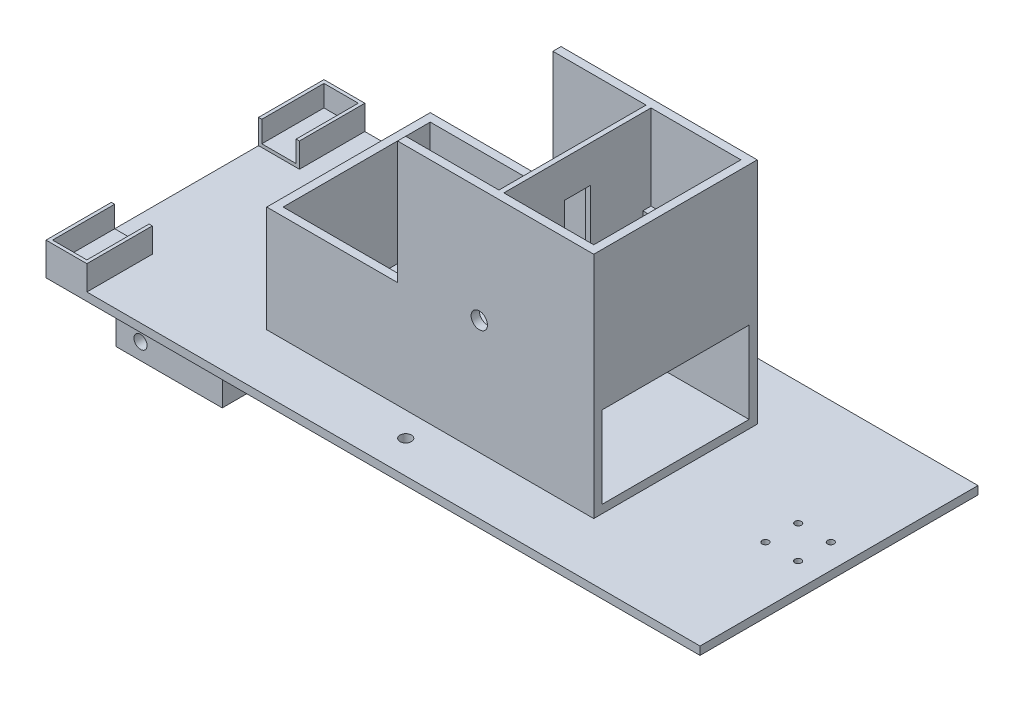
SolidWorks part; units mm, degrees
ref_plane "Front Plane" through (0, 0, 0) normal (0, 0, 1) x (1, 0, 0)
ref_plane "Top Plane" through (0, 0, 0) normal (0, 1, 0) x (1, 0, 0)
ref_plane "Right Plane" through (0, 0, 0) normal (1, 0, 0) x (0, 0, -1)
sketch "Sketch1" plane through (0, 0, 0) normal (0, 1, 0) x (1, 0, 0)
  line L1 (200, -85) -> (-200, -85)
  line L2 (200, -85) -> (200, 85)
  line L3 (200, 85) -> (-200, 85)
  line L4 (-200, -85) -> (-200, 85)
  line L5 (200, -85) -> (-200, 85) construction
  line L6 (200, 85) -> (-200, -85) construction
  point P0 (0, 0)
  dimension "D1" = 170
  dimension "D2" = 400
extrude "Boss-Extrude1" add sketch "Sketch1" along normal blind 5
sketch "Sketch2" plane through (0, 5, 0) normal (0, 1, 0) x (1, 0, 0)
  line L0 (-200, 85) -> (-200, -85) construction
  line L1 (100, -50) -> (-100, -50)
  line L2 (100, -50) -> (100, 50)
  line L3 (100, 50) -> (-100, 50)
  line L4 (-100, -50) -> (-100, 50)
  line L5 (100, -50) -> (-100, 50) construction
  line L6 (100, 50) -> (-100, -50) construction
  point P0 (0, 0)
  dimension "D1" = 200
  dimension "D2" = 100
  dimension "D3" = 200
extrude "Boss-Extrude2" add sketch "Sketch2" along normal blind 140
shell "Shell1" thickness 5 removed face at (0, 145, 0)
sketch "Sketch3" plane through (0, 0, 50) normal (0, 0, 1) x (1, 0, 0)
  line L1 (-100, 145) -> (-20, 145)
  line L2 (-100, 145) -> (-100, 70)
  line L3 (-100, 70) -> (-20, 70)
  line L4 (-20, 145) -> (-20, 70)
  dimension "D1" = 80
  dimension "D2" = 75
extrude "Cut-Extrude1" cut sketch "Sketch3" against normal through all and the other way through all
sketch "Sketch4" plane through (0, 5, 0) normal (0, 1, 0) x (1, 0, 0)
  line L0 (-95, -45) -> (-95, 45) construction
  circle A0 centre (-40, 0) radius 10
  dimension "D1" = 55
extrude "Cut-Extrude2" cut sketch "Sketch4" against normal blind 140
sketch "Sketch5" plane through (0, 0, 50) normal (0, 0, 1) x (1, 0, 0)
  line L0 (-20, 145) -> (100, 145) construction
  line L1 (37, 145) -> (40, 145)
  line L2 (37, 145) -> (37, 5)
  line L3 (37, 5) -> (40, 5)
  line L4 (40, 145) -> (40, 5)
  line L5 (-100, 5) -> (100, 5) construction
  line L6 (100, 145) -> (100, 5) construction
  dimension "D1" = 3
  dimension "D2" = 60
extrude "Boss-Extrude3" add sketch "Sketch5" against normal up to surface (95 mm away) up to face at (-6.6667, 73.3333, -45)
sketch "Sketch6" plane through (37, 0, 0) normal (-1, 0, 0) x (0, 0, 1)
  line L0 (-45, 145) -> (45, 145) construction
  line L1 (8, 27.5) -> (-8, 27.5)
  line L2 (8, 27.5) -> (8, 122.5)
  line L3 (8, 122.5) -> (-8, 122.5)
  line L4 (-8, 27.5) -> (-8, 122.5)
  line L5 (8, 27.5) -> (-8, 122.5) construction
  line L6 (8, 122.5) -> (-8, 27.5) construction
  line L7 (-45, 5) -> (-45, 145) construction
  point P0 (0, 75)
  dimension "D1" = 16
  dimension "D2" = 95
  dimension "D3" = 70
  dimension "D4" = 37
extrude "Cut-Extrude3" cut sketch "Sketch6" against normal up to next
sketch "Sketch7" plane through (0, 0, 50) normal (0, 0, 1) x (1, 0, 0)
  line L0 (-100, 5) -> (100, 5) construction
  line L1 (-20, 145) -> (-20, 70) construction
  circle A0 centre (30, 75) radius 5
  dimension "D1" = 70
  dimension "D3" = 10
  dimension "D2" = 50
extrude "Cut-Extrude4" cut sketch "Sketch7" against normal blind 140
sketch "Sketch8" plane through (0, 0, 0) normal (0, -1, 0) x (1, 0, 0)
  line L1 (-162.2005, 80) -> (-97.2005, 80)
  line L2 (-162.2005, 80) -> (-162.2005, 55)
  line L3 (-162.2005, 55) -> (-97.2005, 55)
  line L4 (-97.2005, 80) -> (-97.2005, 55)
  line L5 (-200, 85) -> (200, 85) construction
  dimension "D1" = 25
  dimension "D2" = 5
  dimension "D3" = 65
extrude "Boss-Extrude4" add sketch "Sketch8" along normal blind 20
mirror "Mirror1" about plane through (0, 0, 0) normal (0, 0, 1) of "Boss-Extrude4"
sketch "Sketch9" plane through (0, 5, 0) normal (0, 1, 0) x (1, 0, 0)
  line L0 (200, -85) -> (200, 85) construction
  line L1 (-200, -85) -> (200, -85) construction
  circle A0 centre (185, 10) radius 2
  circle A1 centre (185, -10) radius 2
  circle A2 centre (165, -10) radius 2
  circle A3 centre (165, 10) radius 2
  dimension "D1" = 4
  dimension "D6" = 75
  dimension "D2" = 20
  dimension "D3" = 20
  dimension "D4" = 20
  dimension "D5" = 15
extrude "Cut-Extrude5" cut sketch "Sketch9" against normal blind 20
sketch "Sketch21" plane through (0, 5, 0) normal (0, 1, 0) x (1, 0, 0)
  line L0 (200, 85) -> (-200, 85) construction
  line L1 (-200, -85) -> (200, -85) construction
  circle A0 centre (0, 65) radius 3.5
  circle A1 centre (0, -65) radius 3.5
  dimension "D1" = 7
  dimension "D2" = 7
  dimension "D3" = 20
  dimension "D4" = 20
extrude "Cut-Extrude9" cut sketch "Sketch21" against normal through all
sketch "Sketch22" plane through (0, 0, 80) normal (0, 0, 1) x (1, 0, 0)
  line L0 (-162.2005, -20) -> (-162.2005, 0) construction
  circle A0 centre (-147.2005, -10) radius 4
  dimension "D1" = 8
  dimension "D2" = 15
extrude "Cut-Extrude10" cut sketch "Sketch22" against normal up to surface (160 mm away) up to face at (-129.7005, -10, -80)
sketch "Sketch35" plane through (100, 0, 0) normal (1, 0, 0) x (0, 0, -1)
  line L1 (-50, 145) -> (-50, 5) construction
  line L2 (-85, 5) -> (85, 5) construction
  line L3 (-45, 60) -> (45, 60)
  line L5 (-45, 60) -> (-45, 10)
  line L6 (-45, 10) -> (45, 10)
  line L7 (45, 10) -> (45, 60)
  dimension "D1" = 90
  dimension "D2" = 5
  dimension "D3" = 5
  dimension "D4" = 50
extrude "Cut-Extrude14" cut sketch "Sketch35" against normal blind 15
sketch "Sketch36" plane through (100, 0, 0) normal (1, 0, 0) x (0, 0, -1)
  line L0 (50, 145) -> (50, 5) construction
  line L1 (-50, 5) -> (50, 5)
  line L2 (-50, 5) -> (-50, 10)
  line L3 (-50, 10) -> (50, 10)
  line L4 (50, 5) -> (50, 10)
extrude "Boss-Extrude17" add sketch "Sketch36" against normal up to surface (60 mm away) up to face at (40, 75, 0)
sketch "Sketch38" plane through (0, 5, 0) normal (0, 1, 0) x (1, 0, 0)
  line L1 (-175, 85) -> (-200, 85)
  line L2 (-175, 85) -> (-175, 45)
  line L3 (-175, 45) -> (-200, 45)
  line L4 (-200, 85) -> (-200, 45)
  line L5 (-175, -85) -> (-200, -85)
  line L6 (-175, -85) -> (-175, -45)
  line L7 (-175, -45) -> (-200, -45)
  line L8 (-200, -85) -> (-200, -45)
  point P8 (0, 0)
  point P9 (-200, 85)
  point P10 (-162.9424, -80.3865)
  point P11 (-200, -85)
  point P12 (0, 0)
  dimension "D1" = 25
  dimension "D2" = 40
extrude "Boss-Extrude19" add sketch "Sketch38" along normal blind 15
sketch "Sketch39" plane through (0, 0, -45) normal (0, 0, 1) x (1, 0, 0)
  line L0 (-200, 20) -> (-175, 20) construction
  line L1 (-198, 20) -> (-177, 20)
  line L2 (-198, 20) -> (-198, 7)
  line L3 (-198, 7) -> (-177, 7)
  line L4 (-177, 20) -> (-177, 7)
  line L5 (-175, 20) -> (-175, 5) construction
  line L6 (-200, 20) -> (-200, 5) construction
  line L7 (-200, 5) -> (-175, 5) construction
  point P12 (-187.5, 5)
  dimension "D1" = 2
  dimension "D2" = 2
  dimension "D3" = 2
extrude "Cut-Extrude15" cut sketch "Sketch39" against normal blind 38 and the other way blind 128
sketch "Sketch41" plane through (0, 0, 50) normal (0, 0, 1) x (1, 0, 0)
  line L0 (40, 145) -> (40, 10) construction
  line L1 (40, 93) -> (95, 93)
  line L2 (40, 93) -> (40, 90)
  line L3 (40, 90) -> (95, 90)
  line L4 (95, 93) -> (95, 90)
  line L5 (95, 145) -> (95, 60) construction
  line L6 (-20, 145) -> (100, 145) construction
  dimension "D1" = 3
  dimension "D2" = 52
extrude "Boss-Extrude20" add sketch "Sketch41" against normal blind 10
mirror "Mirror2" about plane through (0, 0, 0) normal (0, 0, 1) of "Boss-Extrude20"
sketch "Sketch42" plane through (0, 0, 0) normal (0, -1, 0) x (1, 0, 0)
  line L0 (-22.6152, 28.3359) -> (2.6865, 12.217)
  line L1 (-25.3017, 24.119) -> (0, 8)
  line L2 (2.6865, -12.217) -> (-22.6152, -28.3359)
  line L3 (0, -8) -> (-25.3017, -24.119)
  line L4 (0, 0) -> (-30, 0) construction
  line L6 (-22.6152, 28.3359) -> (-25.3017, 24.119)
  line L8 (-25.3017, -24.119) -> (-22.6152, -28.3359)
  line L9 (2.6865, -12.217) -> (0, -8)
  line L10 (0, 8) -> (2.6865, 12.217)
  line L11 (-25.3017, 24.119) -> (-50.0947, 39.9138) construction
  line L12 (-22.6152, 28.3359) -> (-47.4082, 44.1308) construction
  line L13 (-48.9827, -39.2055) -> (-25.3017, -24.119) construction
  line L14 (-46.2962, -43.4224) -> (-22.6152, -28.3359) construction
  circle A0 centre (-40, 0) radius 10 construction
  point P15 (-23.9585, 26.2275)
  dimension "D1" = 8
  dimension "D2" = 30
  dimension "D5" = 30
  dimension "D6" = 8
  dimension "D7" = 32.5
  dimension "D8" = 32.5
  dimension "D3" = 5
  dimension "D4" = 5
extrude "Boss-Extrude21" add sketch "Sketch42" along normal blind 30
sketch "Sketch43" plane through (0, 0, 0) normal (0, -1, 0) x (1, 0, 0)
  line L0 (200, -85) -> (-200, -85) construction
  line L1 (101.0852, -85) -> (86.0852, -85)
  line L2 (101.0852, -85) -> (101.0852, -60)
  line L3 (101.0852, -60) -> (86.0852, -60)
  line L4 (86.0852, -85) -> (86.0852, -60)
  dimension "D1" = 15
  dimension "D2" = 25
extrude "Boss-Extrude22" add sketch "Sketch43" along normal blind 15
sketch "Sketch44" plane through (0, 0, -85) normal (0, 0, -1) x (-1, 0, 0)
  line L0 (-86.0852, -15) -> (-101.0852, -15) construction
  line L1 (-99.0852, -2) -> (-88.0852, -2)
  line L2 (-99.0852, -2) -> (-99.0852, -13)
  line L3 (-99.0852, -13) -> (-88.0852, -13)
  line L4 (-88.0852, -2) -> (-88.0852, -13)
  line L5 (-99.0852, -2) -> (-88.0852, -13) construction
  line L6 (-99.0852, -13) -> (-88.0852, -2) construction
  line L7 (-86.0852, -15) -> (-86.0852, 0) construction
  point P0 (-93.5852, -7.5)
  dimension "D1" = 2
  dimension "D2" = 11
  dimension "D3" = 11
  dimension "D4" = 2
extrude "Cut-Extrude16" cut sketch "Sketch44" against normal up to next
sketch "Sketch45" plane through (0, 0, -85) normal (0, 0, -1) x (-1, 0, 0)
  circle A0 centre (-93.5852, -7.5) radius 5.5
extrude "Boss-Extrude23" add sketch "Sketch45" against normal blind 25 separate body
sketch "Sketch46" plane through (0, 0, -85) normal (0, 0, -1) x (-1, 0, 0)
  circle A0 centre (-93.5852, -7.5) radius 2.5
extrude "Cut-Extrude17" cut sketch "Sketch46" against normal blind 12
